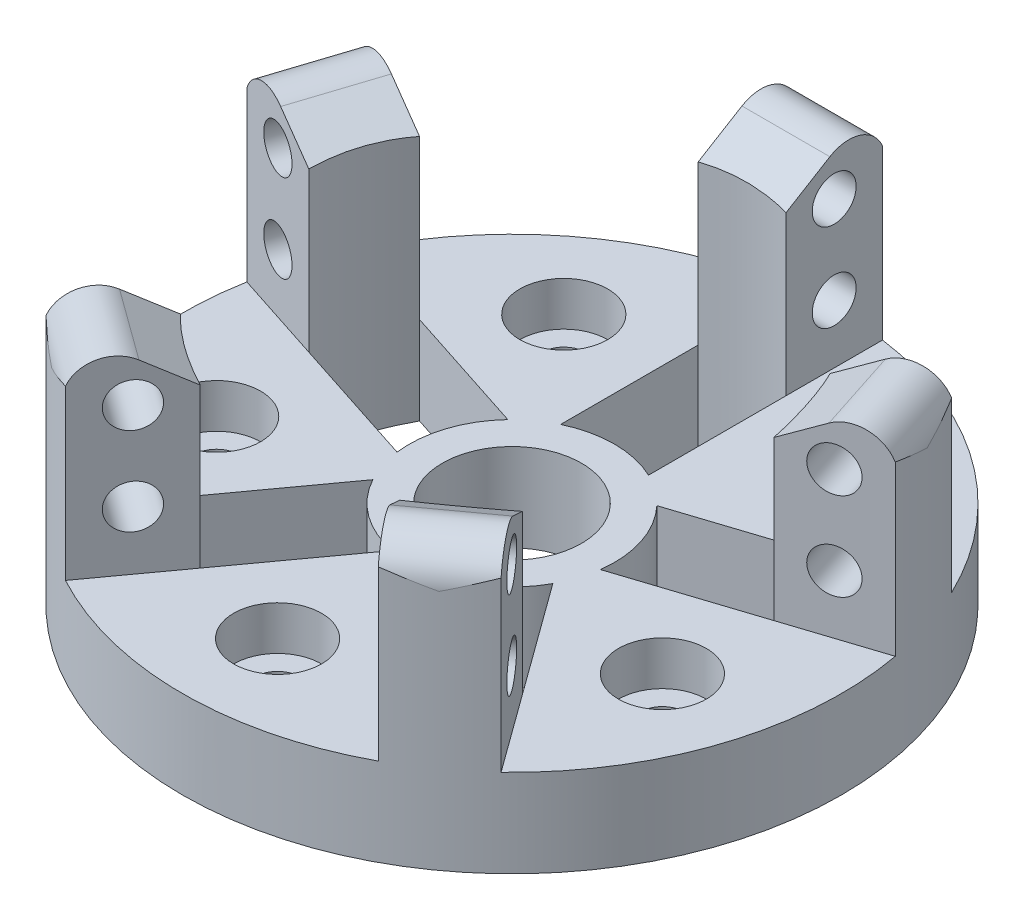
SolidWorks part; units mm, degrees
ref_plane "前视基准面" through (0, 0, 0) normal (0, 0, 1) x (1, 0, 0)
ref_plane "上视基准面" through (0, 0, 0) normal (0, 1, 0) x (1, 0, 0)
ref_plane "右视基准面" through (0, 0, 0) normal (1, 0, 0) x (0, 0, -1)
other "Configuration Table"
sketch "草图1" plane through (0, 0, 0) normal (0, 1, 0) x (1, 0, 0)
  line L0 (11.2688, 8.3075) -> (28.7768, 13.9962)
  line L1 (-4.4187, 13.2844) -> (-4.4187, 31.6935)
  line L2 (0, 14) -> (0, 32) construction
  line L3 (4.4187, 13.2844) -> (4.4187, 31.6935)
  line L4 (13.9997, -0.0973) -> (31.5077, 5.5914)
  line L5 (11.3832, -8.1501) -> (22.2037, -23.0433)
  line L6 (4.2336, -13.3445) -> (15.0541, -28.2378)
  line L7 (-4.2336, -13.3445) -> (-15.0541, -28.2378)
  line L8 (-11.3832, -8.1501) -> (-22.2037, -23.0433)
  line L9 (-13.9997, -0.0973) -> (-31.5077, 5.5914)
  line L10 (-11.2688, 8.3075) -> (-28.7768, 13.9962)
  circle A0 centre (0, 0) radius 45
  arc A1 (4.4187, 31.6935) -> (-4.4187, 31.6935) centre (0, 0) ccw
  arc A2 (4.4187, 13.2844) -> (-4.4187, 13.2844) centre (0, 0) ccw
  arc A3 (31.5077, 5.5914) -> (28.7768, 13.9962) centre (0, 0) ccw
  arc A4 (13.9997, -0.0973) -> (11.2688, 8.3075) centre (0, 0) ccw
  arc A5 (15.0541, -28.2378) -> (22.2037, -23.0433) centre (0, 0) ccw
  arc A6 (4.2336, -13.3445) -> (11.3832, -8.1501) centre (0, 0) ccw
  arc A7 (-22.2037, -23.0433) -> (-15.0541, -28.2378) centre (0, 0) ccw
  arc A8 (-11.3832, -8.1501) -> (-4.2336, -13.3445) centre (0, 0) ccw
  arc A9 (-28.7768, 13.9962) -> (-31.5077, 5.5914) centre (0, 0) ccw
  arc A10 (-11.2688, 8.3075) -> (-13.9997, -0.0973) centre (0, 0) ccw
  circle A11 centre (0, -32) radius 3
  circle A12 centre (-30.4338, -9.8885) radius 3
  circle A13 centre (-18.8091, 25.8885) radius 3
  circle A14 centre (18.8091, 25.8885) radius 3
  circle A15 centre (30.4338, -9.8885) radius 3
  circle A16 centre (0, 0) radius 9.5
  point P27 (0, 0)
  point P39 (0, 0)
  dimension "D1" = 90
  dimension "D2" = 64
  dimension "D3" = 28
  dimension "D5" = 6
  dimension "D8" = 19
  dimension "D6" = 32
  dimension "D4" = 5
  dimension "D7" = 5
extrude "凸台-拉伸1" add sketch "草图1" along normal blind 12
sketch "草图2" plane through (0, 0, 0) normal (1, 0, 0) x (0, 0, -1)
  line L1 (45, 12) -> (45, 33)
  line L3 (-45, 0) -> (45, 0) construction
  line L5 (45, 12) -> (28.7586, 12)
  line L6 (31.6935, 12) -> (13.2844, 12) construction
  line L7 (37.4096, 37.2766) -> (28.7586, 32.0366)
  line L8 (28.7586, 12) -> (28.7586, 32.0366)
  circle A0 centre (38, 32) radius 3
  circle A1 centre (38, 20) radius 3
  arc A2 (45, 33) -> (37.4096, 37.2766) centre (40, 33) ccw
  dimension "D5" = 6
  dimension "D6" = 6
  dimension "D9" = 5
  dimension "D2" = 21
  dimension "D4" = 38
  dimension "D7" = 12
  dimension "D8" = 20
extrude "凸台-拉伸2" add sketch "草图2" along normal mid plane 12
sketch "草图3" plane through (0, 12, 0) normal (0, -1, 0) x (1, 0, 0)
  circle A0 centre (0, 0) radius 32
  circle A1 centre (0, 0) radius 57.9351
  circle A2 centre (0, 0) radius 45
ref_axis "基准轴1" through (0, 12, 0) along (0, 1, 0)
pattern_circular "阵列(圆周)1" count 5 over 360 about axis through (0, 12, 0) along (0, 1, 0) of "凸台-拉伸2"
extrude "切除-拉伸1" cut sketch "草图3" against normal through all contours A0
extrude "切除-拉伸2" cut sketch "草图3<4>" against normal through all contours A1 A2 region at (-56.2964, 12, 0)
sketch "草图3<4>" plane through (0, 12, 0) normal (0, -1, 0) x (1, 0, 0) same geometry as "草图3"
sketch "草图4" plane through (0, 12, 0) normal (0, 1, 0) x (1, 0, 0)
  circle A0 centre (30.4338, -9.8885) radius 6
  circle A1 centre (0, -32) radius 6
  circle A2 centre (-30.4338, -9.8885) radius 6
  circle A3 centre (-18.8091, 25.8885) radius 6
  circle A4 centre (18.8091, 25.8885) radius 6
  point P13 (0, 0)
  dimension "D1" = 12
  dimension "D2" = 5
extrude "切除-拉伸3" cut sketch "草图4" against normal blind 6
sketch "草图5" plane through (0, 12, 0) normal (0, 1, 0) x (1, 0, 0)
  line L0 (6, 31.4325) -> (6, 12.6491)
  line L1 (-6, 31.4325) -> (-6, 12.6491)
  line L2 (31.7482, 4.0068) -> (13.8841, -1.7975)
  line L3 (28.04, 15.4195) -> (10.1759, 9.6151)
  line L4 (13.6214, -28.9561) -> (2.5809, -13.7601)
  line L5 (23.3296, -21.9027) -> (12.2891, -6.7066)
  line L6 (-23.3296, -21.9027) -> (-12.2891, -6.7066)
  line L7 (-13.6214, -28.9561) -> (-2.5809, -13.7601)
  line L8 (-28.04, 15.4195) -> (-10.1759, 9.6151)
  line L9 (-31.7482, 4.0068) -> (-13.8841, -1.7975)
  arc A0 (6, 31.4325) -> (-6, 31.4325) centre (0, 0) ccw construction
  arc A1 (6, 31.4325) -> (-6, 31.4325) centre (0, 0) ccw
  arc A2 (6, 12.6491) -> (-6, 12.6491) centre (0, 0) ccw
  arc A3 (13.8841, -1.7975) -> (10.1759, 9.6151) centre (0, 0) ccw
  arc A4 (31.7482, 4.0068) -> (28.04, 15.4195) centre (0, 0) ccw
  arc A5 (2.5809, -13.7601) -> (12.2891, -6.7066) centre (0, 0) ccw
  arc A6 (13.6214, -28.9561) -> (23.3296, -21.9027) centre (0, 0) ccw
  arc A7 (-12.2891, -6.7066) -> (-2.5809, -13.7601) centre (0, 0) ccw
  arc A8 (-23.3296, -21.9027) -> (-13.6214, -28.9561) centre (0, 0) ccw
  arc A9 (-10.1759, 9.6151) -> (-13.8841, -1.7975) centre (0, 0) ccw
  arc A10 (-28.04, 15.4195) -> (-31.7482, 4.0068) centre (0, 0) ccw
  point P28 (0, 0)
  dimension "D1" = 5
extrude "切除-拉伸4" cut sketch "草图5" against normal through all
